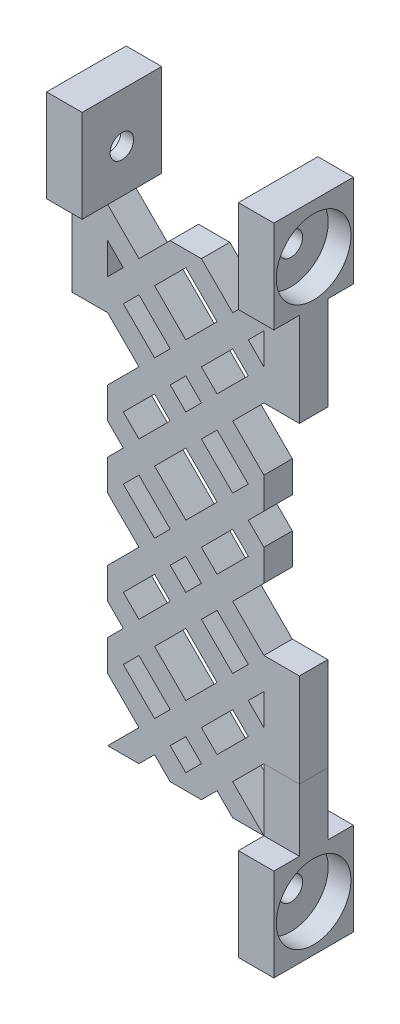
SolidWorks part; units mm, degrees
ref_plane "Front Plane" through (0, 0, 0) normal (0, 0, 1) x (1, 0, 0)
ref_plane "Top Plane" through (0, 0, 0) normal (0, 1, 0) x (1, 0, 0)
ref_plane "Right Plane" through (0, 0, 0) normal (1, 0, 0) x (0, 0, -1)
sketch "Sketch1" plane through (0, 0, 0) normal (1, 0, 0) x (0, 0, -1)
  circle A0 centre (0, 0) radius 15.2785
  dimension "D1" = 30.557
sketch "Sketch2" plane through (0, 0, 0) normal (0, 0, 1) x (1, 0, 0)
  line L0 (0, 0) -> (0, 16.5) construction
  line L1 (0, 16.5) -> (-5.5, 16.5) construction
  line L2 (-27.5, 170.5) -> (-27.5, 181.5)
  line L7 (-27.5, 16.5) -> (-16.5, 16.5)
  line L8 (-27.5, 38.5) -> (-27.5, 49.5)
  line L10 (27.5, 38.5) -> (27.5, 49.5)
  line L13 (-27.5, 181.5) -> (-16.5, 170.5)
  line L14 (22, 121) -> (16.5, 115.5)
  line L15 (-22, 66) -> (-16.5, 60.5)
  line L20 (27.5, 170.5) -> (27.5, 181.5)
  line L22 (0, 176) -> (11, 165)
  line L23 (27.5, 148.5) -> (16.5, 137.5)
  line L24 (-27.5, 93.5) -> (-16.5, 82.5)
  line L25 (-5.5, 181.5) -> (5.5, 181.5) construction
  line L26 (5.5, 181.5) -> (16.5, 170.5)
  line L27 (22, 154) -> (11, 143)
  line L28 (-22, 99) -> (-11, 88)
  line L31 (-5.5, 181.5) -> (5.5, 181.5)
  line L34 (27.5, 170.5) -> (22, 165)
  line L35 (-27.5, 115.5) -> (-22, 110)
  line L37 (27.5, 181.5) -> (16.5, 170.5)
  line L38 (-22, 121) -> (-16.5, 115.5)
  line L39 (22, 66) -> (16.5, 60.5)
  line L44 (0, 176) -> (-11, 165)
  line L45 (-27.5, 148.5) -> (-16.5, 137.5)
  line L46 (27.5, 93.5) -> (16.5, 82.5)
  line L47 (-5.5, 181.5) -> (-16.5, 170.5)
  line L48 (-22, 154) -> (-11, 143)
  line L49 (22, 99) -> (11, 88)
  line L51 (-27.5, 170.5) -> (-22, 165)
  line L52 (27.5, 115.5) -> (22, 110)
  line L53 (-27.5, 60.5) -> (-22, 55)
  line L54 (-22, 44) -> (-11, 33)
  line L55 (-27.5, 38.5) -> (-16.5, 27.5)
  line L57 (27.5, 60.5) -> (22, 55)
  line L58 (22, 44) -> (11, 33)
  line L59 (27.5, 38.5) -> (16.5, 27.5)
  line L61 (11, 22) -> (16.5, 16.5)
  line L62 (16.5, 27.5) -> (27.5, 16.5)
  line L63 (-5.5, 16.5) -> (5.5, 16.5)
  line L64 (16.5, 49.5) -> (5.5, 38.5)
  line L65 (11, 55) -> (0, 44)
  line L66 (16.5, 16.5) -> (27.5, 16.5)
  line L67 (0, 66) -> (-11, 55)
  line L68 (-5.5, 71.5) -> (-16.5, 60.5)
  line L69 (-11, 77) -> (-22, 66)
  line L70 (-16.5, 82.5) -> (-27.5, 71.5)
  line L71 (-16.5, 16.5) -> (-27.5, 16.5) construction
  line L72 (-16.5, 104.5) -> (-5.5, 93.5)
  line L73 (-11, 110) -> (0, 99)
  line L74 (27.5, 60.5) -> (27.5, 71.5)
  line L75 (0, 121) -> (11, 110)
  line L76 (5.5, 126.5) -> (16.5, 115.5)
  line L77 (11, 132) -> (22, 121)
  line L78 (16.5, 137.5) -> (27.5, 126.5)
  line L79 (27.5, 93.5) -> (27.5, 104.5)
  line L80 (16.5, 159.5) -> (5.5, 148.5)
  line L81 (11, 165) -> (0, 154)
  line L82 (-27.5, 93.5) -> (-27.5, 104.5)
  line L83 (-11, 22) -> (-16.5, 16.5)
  line L84 (-16.5, 27.5) -> (-27.5, 16.5)
  line L85 (-27.5, 60.5) -> (-27.5, 71.5)
  line L86 (-16.5, 49.5) -> (-5.5, 38.5)
  line L87 (-11, 55) -> (0, 44)
  line L88 (-27.5, 115.5) -> (-27.5, 126.5)
  line L89 (0, 66) -> (11, 55)
  line L90 (5.5, 71.5) -> (16.5, 60.5)
  line L91 (11, 77) -> (22, 66)
  line L92 (16.5, 82.5) -> (27.5, 71.5)
  line L93 (-27.5, 148.5) -> (-27.5, 159.5)
  line L94 (16.5, 104.5) -> (5.5, 93.5)
  line L95 (11, 110) -> (0, 99)
  line L96 (27.5, 115.5) -> (27.5, 126.5)
  line L97 (0, 121) -> (-11, 110)
  line L98 (-5.5, 126.5) -> (-16.5, 115.5)
  line L99 (-11, 132) -> (-22, 121)
  line L100 (-16.5, 137.5) -> (-27.5, 126.5)
  line L101 (27.5, 148.5) -> (27.5, 159.5)
  line L102 (-16.5, 159.5) -> (-5.5, 148.5)
  line L103 (-11, 165) -> (0, 154)
  line L105 (-11, 22) -> (-5.5, 16.5)
  line L106 (-5.5, 27.5) -> (0, 22)
  line L107 (0, 33) -> (5.5, 27.5)
  line L108 (5.5, 38.5) -> (11, 33)
  line L110 (16.5, 49.5) -> (22, 44)
  line L111 (22, 55) -> (27.5, 49.5)
  line L113 (11, 77) -> (5.5, 71.5)
  line L114 (5.5, 82.5) -> (0, 77)
  line L115 (0, 88) -> (-5.5, 82.5)
  line L116 (-5.5, 93.5) -> (-11, 88)
  line L118 (-16.5, 104.5) -> (-22, 99)
  line L119 (-22, 110) -> (-27.5, 104.5)
  line L121 (-11, 132) -> (-5.5, 126.5)
  line L122 (-5.5, 137.5) -> (0, 132)
  line L123 (0, 143) -> (5.5, 137.5)
  line L124 (5.5, 148.5) -> (11, 143)
  line L126 (16.5, 159.5) -> (22, 154)
  line L127 (22, 165) -> (27.5, 159.5)
  line L128 (11, 22) -> (5.5, 16.5)
  line L129 (5.5, 27.5) -> (0, 22)
  line L130 (0, 33) -> (-5.5, 27.5)
  line L131 (-5.5, 38.5) -> (-11, 33)
  line L133 (-16.5, 49.5) -> (-22, 44)
  line L134 (-22, 55) -> (-27.5, 49.5)
  line L136 (-11, 77) -> (-5.5, 71.5)
  line L137 (-5.5, 82.5) -> (0, 77)
  line L138 (0, 88) -> (5.5, 82.5)
  line L139 (5.5, 93.5) -> (11, 88)
  line L141 (16.5, 104.5) -> (22, 99)
  line L142 (22, 110) -> (27.5, 104.5)
  line L144 (5.5, 137.5) -> (0, 132)
  line L145 (11, 132) -> (5.5, 126.5)
  line L146 (0, 143) -> (-5.5, 137.5)
  line L147 (-5.5, 148.5) -> (-11, 143)
  line L149 (-16.5, 159.5) -> (-22, 154)
  line L150 (-22, 165) -> (-27.5, 159.5)
  dimension "D1" = 5.5
  dimension "D2" = 55
  dimension "D3" = 27.5
  dimension "D4" = 5.5
  dimension "D5" = 11
  dimension "D6" = 11
  dimension "D7" = 16.5
  dimension "D8" = 16.5
  dimension "D9" = 22
  dimension "D10" = 22
  dimension "D11" = 5.5
  dimension "D12" = 5.5
  dimension "D13" = 11
  dimension "D14" = 11
  dimension "D15" = 16.5
  dimension "D16" = 16.5
  dimension "D17" = 22
  dimension "D18" = 22
  dimension "D19" = 16.5
  dimension "D20" = 27.5
  dimension "D21" = 27.5
  dimension "D22" = 33
  dimension "D23" = 38.5
  dimension "D24" = 38.5
  dimension "D25" = 33
  dimension "D26" = 44
  dimension "D27" = 49.5
  dimension "D28" = 49.5
  dimension "D29" = 55
  dimension "D30" = 55
  dimension "D31" = 66
  dimension "D32" = 66
  dimension "D33" = 71.5
  dimension "D34" = 71.5
  dimension "D35" = 77
  dimension "D36" = 77
  dimension "D37" = 82.5
  dimension "D38" = 99
  dimension "D39" = 99
  dimension "D40" = 104.5
  dimension "D41" = 104.5
  dimension "D42" = 121
  dimension "D43" = 132
extrude "Boss-Extrude1" add sketch "Sketch2" along normal blind 10
sketch "Sketch3" plane through (27.5, 0, 0) normal (1, 0, 0) x (0, 0, -1)
  line L1 (-10, 181.5) -> (0, 181.5)
  line L2 (-10, 181.5) -> (-10, 148.5)
  line L3 (-10, 148.5) -> (0, 148.5)
  line L4 (0, 181.5) -> (0, 148.5)
extrude "Boss-Extrude3" add sketch "Sketch3" along normal blind 12.5
ref_axis "Axis1" through (0, 181.5, 0) along (0, -1, 0)
mirror "Mirror1" about plane through (0, 0, 0) normal (1, 0, 0) of "Boss-Extrude3"
sketch "Sketch4" plane through (0, 181.5, 0) normal (0, 1, 0) x (1, 0, 0)
  line L5 (33.75, 0) -> (33.75, -10) construction
  line L6 (40, 0) -> (27.5, 0) construction
  line L7 (40, -10) -> (27.5, -10) construction
  line L8 (27.5, -5) -> (40, -5) construction
  line L9 (27.5, -10) -> (27.5, 0) construction
  line L10 (40, 0) -> (40, -10) construction
  line L12 (27.5, -19) -> (40, -19)
  line L13 (27.5, -19) -> (27.5, 9)
  line L14 (27.5, 9) -> (40, 9)
  line L15 (40, -19) -> (40, 9)
  line L16 (27.5, -19) -> (40, 9) construction
  line L17 (27.5, 9) -> (40, -19) construction
  point P13 (33.75, -5)
  dimension "D1" = 12.5
  dimension "D2" = 28
extrude "Boss-Extrude4" add sketch "Sketch4" along normal blind 32.6
mirror "Mirror2" about plane through (0, 0, 0) normal (1, 0, 0) of "Boss-Extrude4"
sketch "Sketch6" plane through (-40, 0, 0) normal (-1, 0, 0) x (0, 0, 1)
  line L0 (5, 214.1) -> (5, 196.8) construction
  line L1 (19, 214.1) -> (-9, 214.1) construction
  circle A0 centre (5, 196.8) radius 13.15
  dimension "D1" = 26.3
  dimension "D2" = 17.3
extrude "Cut-Extrude2" cut sketch "Sketch6" against normal blind 8
mirror "Mirror3" about plane through (0, 0, 0) normal (1, 0, 0) of "Cut-Extrude2"
sketch "Sketch7" plane through (-32, 0, 0) normal (-1, 0, 0) x (0, 0, 1)
  line L0 (5, 209.95) -> (5, 183.65) construction
  line L1 (5, 183.65) -> (18.15, 196.8) construction
  line L2 (18.15, 196.8) -> (-8.15, 196.8) construction
  circle A0 centre (5, 196.8) radius 13.15 construction
  circle A1 centre (5, 196.8) radius 13.15 construction
  circle A2 centre (5, 196.8) radius 4.15
  dimension "D1" = 8.3
extrude "Cut-Extrude3" cut sketch "Sketch7" against normal through all
ref_plane "Plane1" through (0, 98.75, 0) normal (0, 1, 0) x (1, 0, 0)
sketch "Sketch8" plane through (27.5, 0, 0) normal (1, 0, 0) x (0, 0, -1)
  line L5 (-10, 71.5) -> (0, 71.5)
  line L6 (-10, 71.5) -> (-10, 38.5)
  line L7 (-10, 38.5) -> (0, 38.5)
  line L8 (0, 71.5) -> (0, 38.5)
extrude "Boss-Extrude6" add sketch "Sketch8" along normal blind 12.5
sketch "Sketch9" plane through (0, 38.5, 0) normal (0, -1, 0) x (1, 0, 0)
  line L0 (33.75, 10) -> (33.75, 0) construction
  line L1 (40, 10) -> (27.5, 10) construction
  line L2 (40, 0) -> (27.5, 0) construction
  line L3 (40, 5) -> (27.5, 5) construction
  line L4 (40, 10) -> (40, 0) construction
  line L5 (27.5, 10) -> (27.5, 0) construction
  line L7 (27.5, 0) -> (40, 0)
  line L8 (27.5, 0) -> (27.5, 10)
  line L9 (27.5, 10) -> (40, 10)
  line L10 (40, 0) -> (40, 10)
  line L11 (27.5, 0) -> (40, 10) construction
  line L12 (27.5, 10) -> (40, 0) construction
  point P12 (33.75, 5)
extrude "Boss-Extrude9" add sketch "Sketch9" along normal blind 22 separate body
sketch "Sketch10" plane through (0, 16.5, 0) normal (0, -1, 0) x (1, 0, 0)
  line L0 (33.75, 10) -> (33.75, 0) construction
  line L1 (40, 10) -> (27.5, 10) construction
  line L2 (27.5, 0) -> (40, 0) construction
  line L3 (33.75, 0) -> (40, 5) construction
  line L4 (40, 0) -> (40, 10) construction
  line L5 (40, 5) -> (27.5, 5) construction
  line L6 (27.5, 10) -> (27.5, 0) construction
  line L8 (27.5, -9) -> (40, -9)
  line L9 (27.5, -9) -> (27.5, 19)
  line L10 (27.5, 19) -> (40, 19)
  line L11 (40, -9) -> (40, 19)
  line L12 (27.5, -9) -> (40, 19) construction
  line L13 (27.5, 19) -> (40, -9) construction
  point P6 (33.75, 5)
extrude "Boss-Extrude10" add sketch "Sketch10" along normal blind 32.6
sketch "Sketch12" plane through (40, 0, 0) normal (1, 0, 0) x (0, 0, -1)
  line L0 (-5, 209.95) -> (-5, 183.65) construction
  line L1 (-18.15, 196.8) -> (8.15, 196.8) construction
  line L2 (-5, 196.8) -> (-5, -16.1) construction
  line L3 (9, -16.1) -> (-19, -16.1) construction
  line L4 (-19, 0.2) -> (9, 0.2) construction
  line L5 (-19, -16.1) -> (-19, 16.5) construction
  line L6 (9, -16.1) -> (9, 16.5) construction
  circle A0 centre (-5, 196.8) radius 13.15 construction
  circle A1 centre (-5, 0.2) radius 13.15
  dimension "D1" = 26.3
extrude "Cut-Extrude4" cut sketch "Sketch12" against normal blind 8
sketch "Sketch13" plane through (32, 0, 0) normal (1, 0, 0) x (0, 0, -1)
  line L0 (-5, 13.35) -> (-5, -12.95) construction
  line L1 (-5, -12.95) -> (8.15, 0.2) construction
  line L2 (8.15, 0.2) -> (-18.15, 0.2) construction
  circle A0 centre (-5, 0.2) radius 13.15 construction
  circle A2 centre (-5, 0.2) radius 4.15
  dimension "D1" = 8.3
extrude "Cut-Extrude5" cut sketch "Sketch13" against normal blind 8
